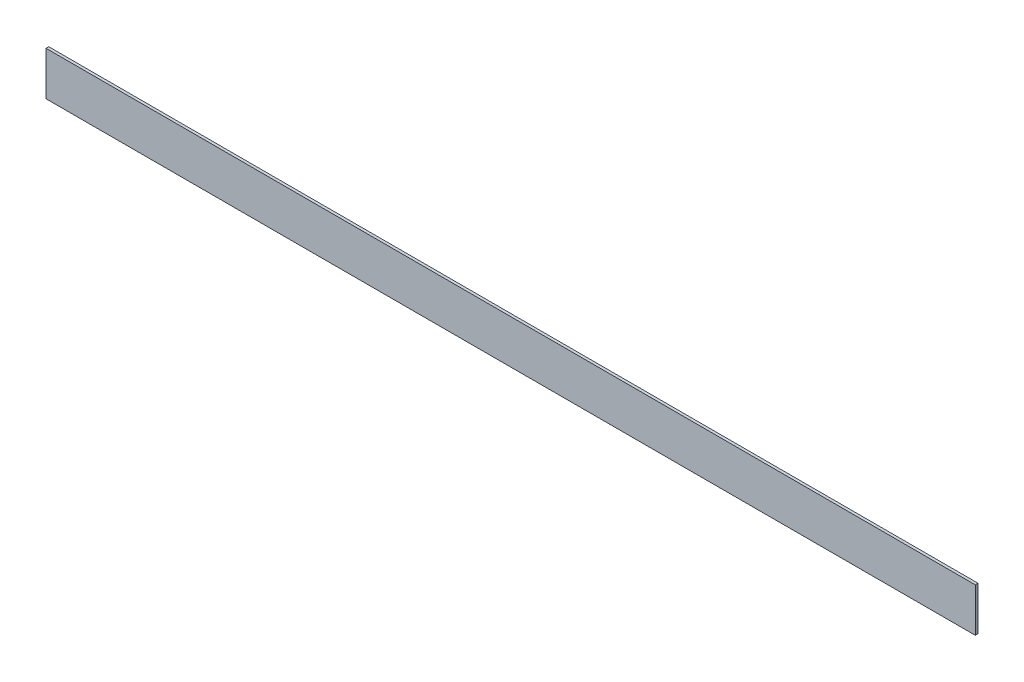
SolidWorks part; units mm, degrees
ref_plane "Front Plane" through (0, 0, 0) normal (0, 0, 1) x (1, 0, 0)
ref_plane "Top Plane" through (0, 0, 0) normal (0, 1, 0) x (1, 0, 0)
ref_plane "Right Plane" through (0, 0, 0) normal (1, 0, 0) x (0, 0, -1)
sketch "Sketch1" plane through (0, 0, 0) normal (0, 0, 1) x (1, 0, 0)
  line L1 (0, 0) -> (539.75, 0)
  line L2 (0, 0) -> (0, 25.4)
  line L3 (0, 25.4) -> (539.75, 25.4)
  line L4 (539.75, 0) -> (539.75, 25.4)
  dimension "D1" = 539.75
  dimension "D2" = 25.4
extrude "Boss-Extrude1" add sketch "Sketch1" along normal blind 1.5875
